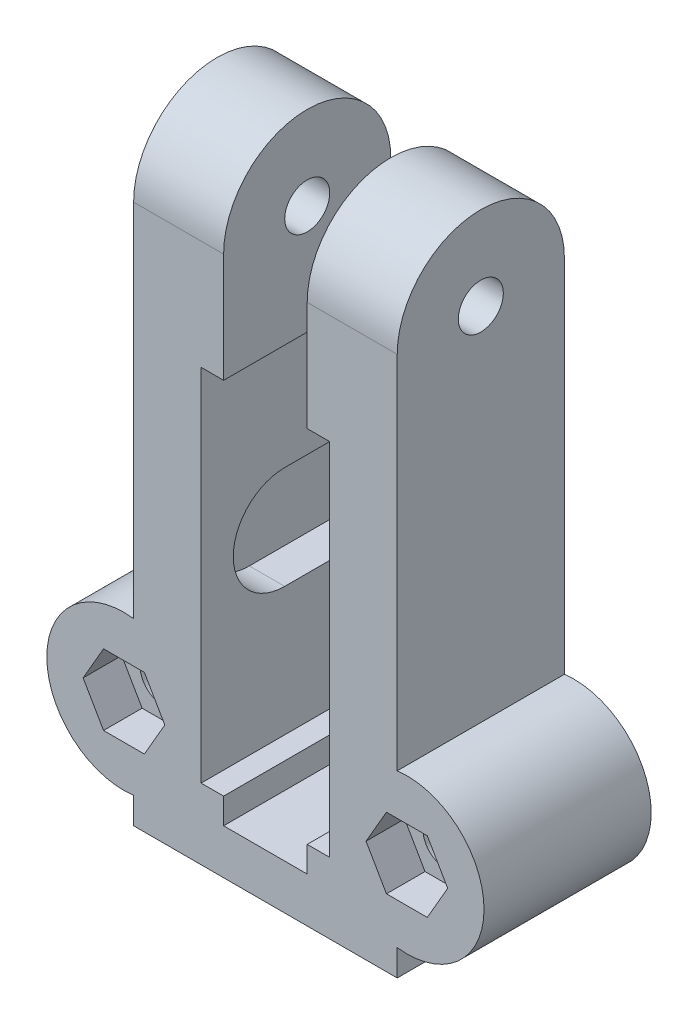
SolidWorks part; units mm, degrees
ref_plane "Front Plane" through (0, 0, 0) normal (0, 0, 1) x (1, 0, 0)
ref_plane "Top Plane" through (0, 0, 0) normal (0, 1, 0) x (1, 0, 0)
ref_plane "Right Plane" through (0, 0, 0) normal (1, 0, 0) x (0, 0, -1)
sketch "Sketch1" plane through (0, 0, 0) normal (0, 0, 1) x (1, 0, 0)
  line L0 (-3.25, 0) -> (-3.25, -45)
  line L1 (-3.25, -45) -> (3.25, -45)
  line L2 (3.25, -45) -> (3.25, 0)
  line L3 (3.25, 0) -> (10.25, 0)
  line L4 (10.25, 0) -> (10.25, -48.5)
  line L5 (10.25, -48.5) -> (-10.25, -48.5)
  line L6 (-10.25, -48.5) -> (-10.25, 0)
  line L7 (-10.25, 0) -> (-3.25, 0)
  dimension "D1" = 6.5
  dimension "D2" = 3.25
  dimension "D3" = 45
  dimension "D4" = 7
  dimension "D5" = 3.5
extrude "Boss-Extrude1" add sketch "Sketch1" along normal blind 13
sketch "Sketch2" plane through (10.25, 0, 0) normal (1, 0, 0) x (0, 0, -1)
  line L0 (-6.5, 0) -> (-6.5, -48.5) construction
  line L1 (-13, 0) -> (0, 0) construction
  line L2 (-13, -48.5) -> (0, -48.5) construction
  line L3 (-13, -6.5) -> (-21.1298, -6.5)
  line L4 (-21.1298, -6.5) -> (-21.1298, 2.8811)
  line L5 (-21.1298, 2.8811) -> (14.28, 2.8811)
  line L6 (14.28, 2.8811) -> (14.28, -6.5)
  line L7 (14.28, -6.5) -> (0, -6.5)
  circle A0 centre (-6.5, -6.5) radius 1.75
  arc A1 (0, -6.5) -> (-13, -6.5) centre (-6.5, -6.5) ccw
  dimension "D1" = 3.5
  dimension "D2" = 13
extrude "Cut-Extrude1" cut sketch "Sketch2" against normal up to surface (20.5 mm away) up to face at (-10.25, -24.25, 6.5)
sketch "Sketch4" plane through (0, 0, 13) normal (0, 0, 1) x (1, 0, 0)
  line L0 (3.25, -45) -> (-3.25, -45) construction
  line L1 (-5, -15) -> (5, -15)
  line L2 (-5, -15) -> (-5, -43)
  line L3 (-5, -43) -> (5, -43)
  line L4 (5, -15) -> (5, -43)
  dimension "D1" = 10
  dimension "D2" = 5
  dimension "D3" = 28
  dimension "D4" = 2
extrude "Cut-Extrude2" cut sketch "Sketch4" against normal blind 13
ref_plane "Plane1" through (0, 0, 0) normal (1, 0, 0) x (0, 0, -1)
sketch "Sketch7" plane through (0, 0, 0) normal (1, 0, 0) x (0, 0, -1)
  line L0 (-6.5, -15) -> (-6.5, -43) construction
  line L1 (0, -15) -> (-13, -15) construction
  line L2 (0, -43) -> (-13, -43) construction
  line L3 (-6.5, -25) -> (0, -25)
  line L4 (0, -48.5) -> (0, -6.5) construction
  line L5 (0, -25) -> (0, -33)
  line L6 (0, -33) -> (-6.5, -33)
  arc A0 (-6.5, -25) -> (-6.5, -33) centre (-6.5, -29) ccw
  circle A1 centre (-6.5, -29) radius 11 construction
  dimension "D1" = 8
  dimension "D2" = 22
extrude "Cut-Extrude3" cut sketch "Sketch7" against normal offset from surface 2.5 and the other way offset from surface 2.5 up to face at (-10.25, -4.75, 6.5) other way up to face at (10.25, -4.75, 6.5)
sketch "Sketch8" plane through (0, 0, 0) normal (0, 0, -1) x (-1, 0, 0)
  line L0 (11, -40.5) -> (-11, -40.5) construction
  line L1 (0, 7.15) -> (0, -7.15) construction
  line L2 (10.25, -48.5) -> (-10.25, -48.5) construction
  circle A0 centre (11, -40.5) radius 6
  circle A1 centre (-11, -40.5) radius 6
  dimension "D1" = 22
  dimension "D3" = 12
  dimension "D2" = 11
  dimension "D4" = 8
extrude "Boss-Extrude2" add sketch "Sketch8" against normal up to surface (13 mm away) up to face at (0, -27.8125, 13)
sketch "Sketch9" plane through (0, 0, 0) normal (0, 0, -1) x (-1, 0, 0)
  circle A0 centre (11, -40.5) radius 1.75
  circle A1 centre (-11, -40.5) radius 1.75
  dimension "D1" = 3.5
extrude "Cut-Extrude4" cut sketch "Sketch9" against normal up to next
sketch "Sketch10" plane through (0, 0, 0) normal (0, 0, -1) x (-1, 0, 0)
  circle A0 centre (11, -40.5) radius 4
  circle A1 centre (-11, -40.5) radius 4
  dimension "D1" = 8
extrude "Cut-Extrude5" cut sketch "Sketch10" against normal blind 3
sketch "Sketch11" plane through (0, 0, 13) normal (0, 0, 1) x (1, 0, 0)
  line L1 (14.1754, -40.5) -> (12.5877, -37.75)
  line L2 (12.5877, -37.75) -> (9.4123, -37.75)
  line L3 (9.4123, -37.75) -> (7.8246, -40.5)
  line L4 (7.8246, -40.5) -> (9.4123, -43.25)
  line L5 (9.4123, -43.25) -> (12.5877, -43.25)
  line L6 (12.5877, -43.25) -> (14.1754, -40.5)
  line L7 (-7.8246, -40.5) -> (-9.4123, -37.75)
  line L8 (-9.4123, -37.75) -> (-12.5877, -37.75)
  line L9 (-12.5877, -37.75) -> (-14.1754, -40.5)
  line L10 (-14.1754, -40.5) -> (-12.5877, -43.25)
  line L11 (-12.5877, -43.25) -> (-9.4123, -43.25)
  line L12 (-9.4123, -43.25) -> (-7.8246, -40.5)
  circle A0 centre (11, -40.5) radius 2.75 construction
  circle A1 centre (-11, -40.5) radius 2.75 construction
  dimension "D1" = 5.5
extrude "Cut-Extrude6" cut sketch "Sketch11" against normal blind 3
